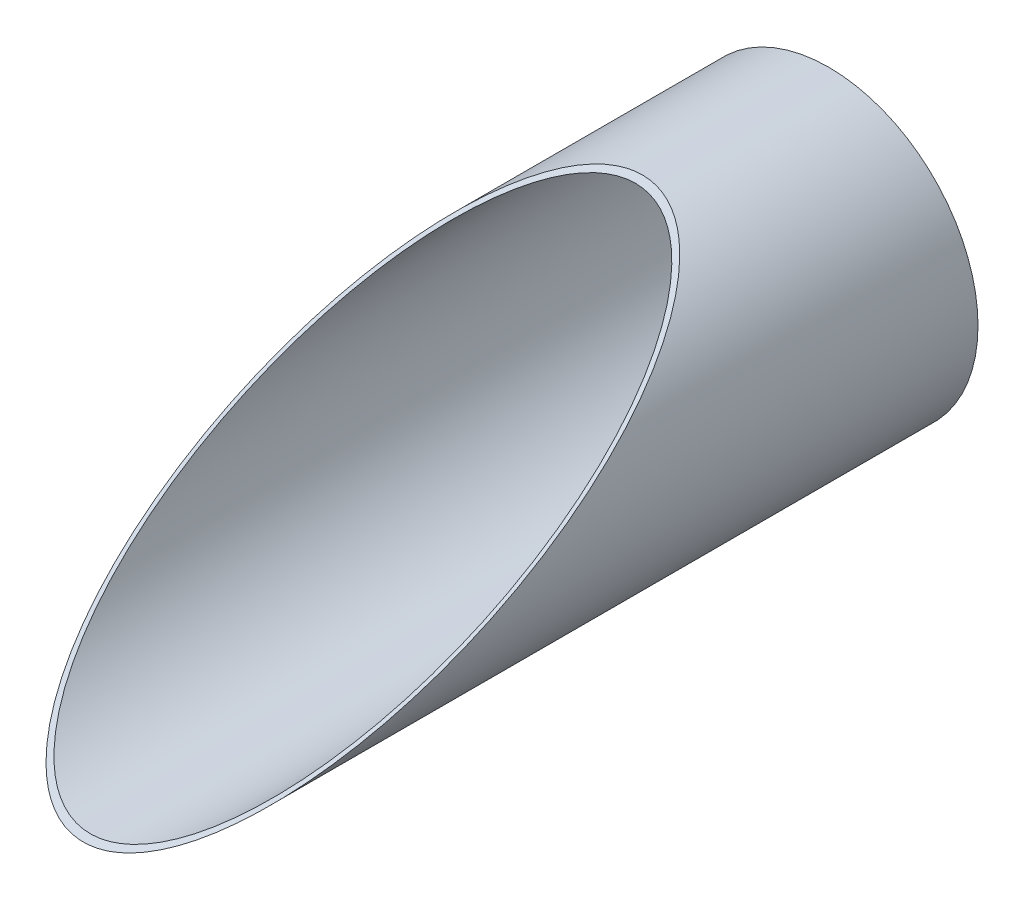
SolidWorks part; units mm, degrees
ref_plane "Front Plane" through (0, 0, 0) normal (0, 0, 1) x (1, 0, 0)
ref_plane "Top Plane" through (0, 0, 0) normal (0, 1, 0) x (1, 0, 0)
ref_plane "Right Plane" through (0, 0, 0) normal (1, 0, 0) x (0, 0, -1)
sketch "Sketch1" plane through (0, 0, 0) normal (0, 0, 1) x (1, 0, 0)
  circle A0 centre (0, 0) radius 20
  dimension "D1" = 40
extrude "Boss-Extrude1" add sketch "Sketch1" along normal blind 100 contours A0
sketch "Sketch2" plane through (0, 0, 0) normal (1, 0, 0) x (0, 0, -1)
  line L0 (-100, -20) -> (-25, 20)
  line L1 (0, 20) -> (-100, 20) construction
  line L2 (-25, 20) -> (-100, 20)
  line L3 (-100, 20) -> (-100, -20)
  line L4 (0, -20) -> (0, 20) construction
  dimension "D1" = 25
extrude "Cut-Extrude1" cut sketch "Sketch2" against normal through all both and the other way through all
shell "Shell1" thickness 0.5 removed face at (20, 0, 0) removed face at (0, 20, 25)
